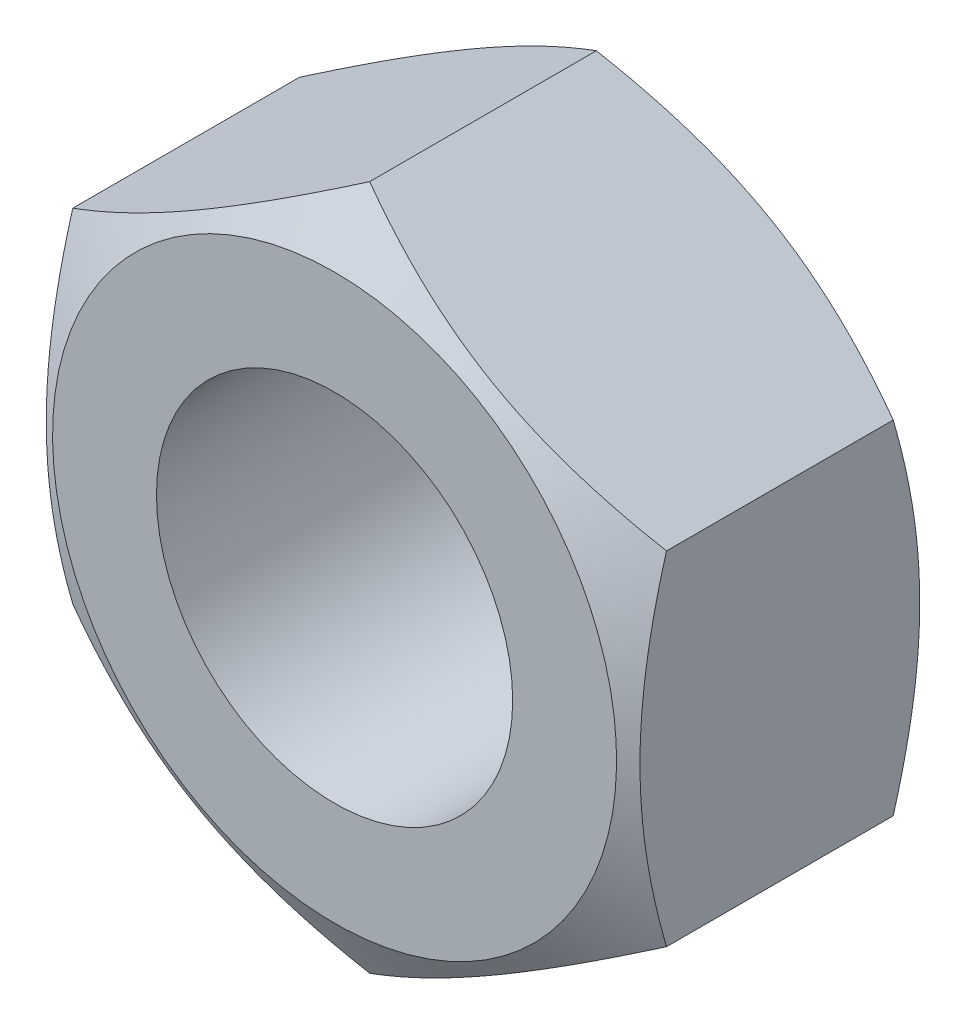
SolidWorks part; units mm, degrees
ref_plane "Спереди" through (0, 0, 0) normal (0, 0, 1) x (1, 0, 0)
ref_plane "Сверху" through (0, 0, 0) normal (0, 1, 0) x (1, 0, 0)
ref_plane "Справа" through (0, 0, 0) normal (1, 0, 0) x (0, 0, -1)
sketch "Эскиз1" plane through (0, 0, 0) normal (0, 0, 1) x (1, 0, 0)
  line L1 (0, 1.1547) -> (-1, 0.5774)
  line L2 (-1, 0.5774) -> (-1, -0.5774)
  line L3 (-1, -0.5774) -> (0, -1.1547)
  line L4 (0, -1.1547) -> (1, -0.5774)
  line L5 (1, -0.5774) -> (1, 0.5774)
  line L6 (1, 0.5774) -> (0, 1.1547)
  circle A0 centre (0, 0) radius 1 construction
  circle A1 centre (0, 0) radius 0.6
extrude "Бобышка-Вытянуть1" add sketch "Эскиз1" along normal blind 1
sketch "Эскиз2" plane through (0, 0, 0) normal (1, 0, 0) x (0, 0, -1)
  line L0 (0, 0) -> (0, 0.95)
  line L1 (0, 0.95) -> (-0.219, 1.3293)
  line L3 (0, 1.3293) -> (0, 0.95)
  line L4 (0, 0) -> (-1, 0)
  line L5 (-1, -0.5774) -> (-1, 0.5774) construction
  line L6 (-0.5, 0) -> (-0.5, -1.783)
  line L7 (0, 1.3293) -> (-0.219, 1.3293)
  line L8 (-1, 1.3293) -> (-0.781, 1.3293)
  line L9 (-1, 1.3293) -> (-1, 0.95)
  line L10 (-1, 0.95) -> (-0.781, 1.3293)
revolve "Вырез-Повернуть1" cut sketch "Эскиз2" angle 360 about L4 region at (0, 1.2029, 0.073) region at (0, 1.2029, 0.927)
